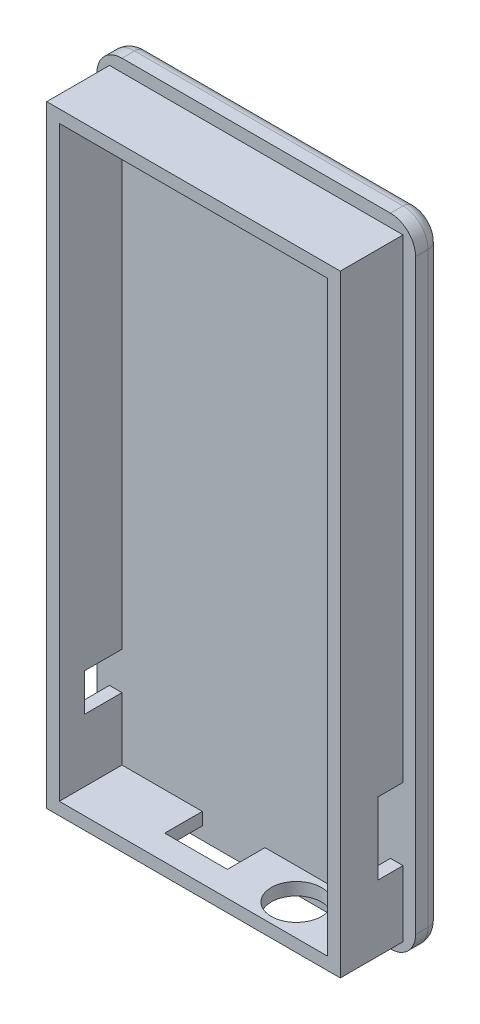
SolidWorks part; units mm, degrees
ref_plane "Front Plane" through (0, 0, 0) normal (0, 0, 1) x (1, 0, 0)
ref_plane "Top Plane" through (0, 0, 0) normal (0, 1, 0) x (1, 0, 0)
ref_plane "Right Plane" through (0, 0, 0) normal (1, 0, 0) x (0, 0, -1)
sketch "Sketch2" plane through (0, 0, 0) normal (0, 0, 1) x (1, 0, 0)
  line L1 (0, 0) -> (25.4, 0)
  line L2 (0, 0) -> (0, 50.8)
  line L3 (0, 50.8) -> (25.4, 50.8)
  line L4 (25.4, 0) -> (25.4, 50.8)
  dimension "D1" = 25.4
  dimension "D2" = 50.8
extrude "Boss-Extrude1" add sketch "Sketch2" along normal blind 2
sketch "Sketch3" plane through (0, 0, 2) normal (0, 0, 1) x (1, 0, 0)
  line L0 (25.4, 50.8) -> (0, 50.8) construction
  line L1 (1, 49.8) -> (24.4, 49.8)
  line L2 (1, 49.8) -> (1, 1)
  line L3 (1, 1) -> (24.4, 1)
  line L4 (24.4, 49.8) -> (24.4, 1)
  line L5 (2, 48.8) -> (23.4, 48.8)
  line L6 (2, 48.8) -> (2, 2)
  line L7 (2, 2) -> (23.4, 2)
  line L8 (23.4, 48.8) -> (23.4, 2)
  line L9 (0, 50.8) -> (0, 0) construction
  line L10 (0, 0) -> (25.4, 0) construction
  line L11 (25.4, 0) -> (25.4, 50.8) construction
  line L12 (25.4, 50.8) -> (0, 50.8)
  line L13 (0, 50.8) -> (0, 0)
  line L14 (0, 0) -> (25.4, 0)
  line L15 (25.4, 0) -> (25.4, 50.8)
  dimension "D1" = 1
  dimension "D2" = 1
  dimension "D3" = 1
  dimension "D4" = 1
  dimension "D5" = 1
  dimension "D6" = 1
  dimension "D7" = 1
  dimension "D8" = 1
extrude "Boss-Extrude2" add sketch "Sketch3" along normal blind 5 contours L4 L1 L2 L3 L5 L8 L7 L6 region at (12.7, 49.2588, 2)
fillet "Fillet1" radius 2 4 edges at (0, 50.8, 1) (0, 0, 1) (25.4, 0, 1) (25.4, 50.8, 1)
fillet "Fillet2" radius 1 8 edges at (0.5858, 0.5858, 0) (12.7, 0, 0) (24.8142, 0.5858, 0) (25.4, 25.4, 0) (24.8142, 50.2142, 0) (12.7, 50.8, 0) (0.5858, 50.2142, 0) (0, 25.4, 0)
sketch "Sketch4" plane through (24.4, 0, 0) normal (1, 0, 0) x (0, 0, -1)
  line L0 (-2, 49.8) -> (-2, 1) construction
  line L1 (-2, 6.2576) -> (-4, 6.2576)
  line L2 (-2, 6.2576) -> (-2, 12)
  line L3 (-2, 12) -> (-4, 12)
  line L4 (-4, 6.2576) -> (-4, 12)
extrude "Cut-Extrude1" cut sketch "Sketch4" against normal up to next
sketch "Sketch5" plane through (0, 1, 0) normal (0, -1, 0) x (1, 0, 0)
  circle A0 centre (18.4, 4.5) radius 2
extrude "Cut-Extrude2" cut sketch "Sketch5" against normal up to next
sketch "Sketch6" plane through (0, 1, 0) normal (0, -1, 0) x (1, 0, 0)
  line L0 (8.4, 5) -> (8.4, 2) construction
  line L1 (13.4, 5) -> (8.4, 5)
  line L2 (13.4, 5) -> (13.4, 2)
  line L3 (13.4, 2) -> (8.4, 2)
  line L4 (8.4, 5) -> (8.4, 2)
  line L5 (1, 2) -> (24.4, 2) construction
extrude "Cut-Extrude3" cut sketch "Sketch6" against normal up to next
sketch "Sketch7" plane through (1, 0, 0) normal (-1, 0, 0) x (0, 0, 1)
  line L0 (2, 49.8) -> (2, 1) construction
  line L1 (2, 10) -> (5, 10)
  line L2 (2, 10) -> (2, 7)
  line L3 (2, 7) -> (5, 7)
  line L4 (5, 10) -> (5, 7)
  line L5 (5, 10) -> (2, 10) construction
  line L6 (2, 7) -> (5, 7) construction
  line L7 (5, 7) -> (5, 10) construction
extrude "Cut-Extrude4" cut sketch "Sketch7" against normal up to next
equation "\"width\"=1"
equation "\"D1@Sketch2\"=\"width\""
equation "\"length\"=2"
equation "\"D2@Sketch2\"=\"length\""
equation "\"container_thickness\"=0.0787402"
equation "\"D1@Boss-Extrude1\"=\"container_thickness\""
equation "\"lip_thickness\"=0.0393701"
equation "\"D1@Sketch3\"=\"lip_thickness\""
equation "\"D2@Sketch3\"=\"lip_thickness\""
equation "\"D3@Sketch3\"=\"lip_thickness\""
equation "\"D4@Sketch3\"=\"lip_thickness\""
equation "\"D5@Sketch3\"=\"lip_thickness\""
equation "\"D6@Sketch3\"=\"lip_thickness\""
equation "\"D7@Sketch3\"=\"lip_thickness\""
equation "\"D8@Sketch3\"=\"lip_thickness\""
equation "\"lip_height\"= 5mm"
equation "\"D1@Boss-Extrude2\"=\"lip_height\""
equation "\"side_fillet\"= 2mm"
equation "\"D1@Fillet1\"=\"side_fillet\""
equation "\"face_fillet\"= 1mm"
equation "\"D1@Fillet2\"=\"face_fillet\""
